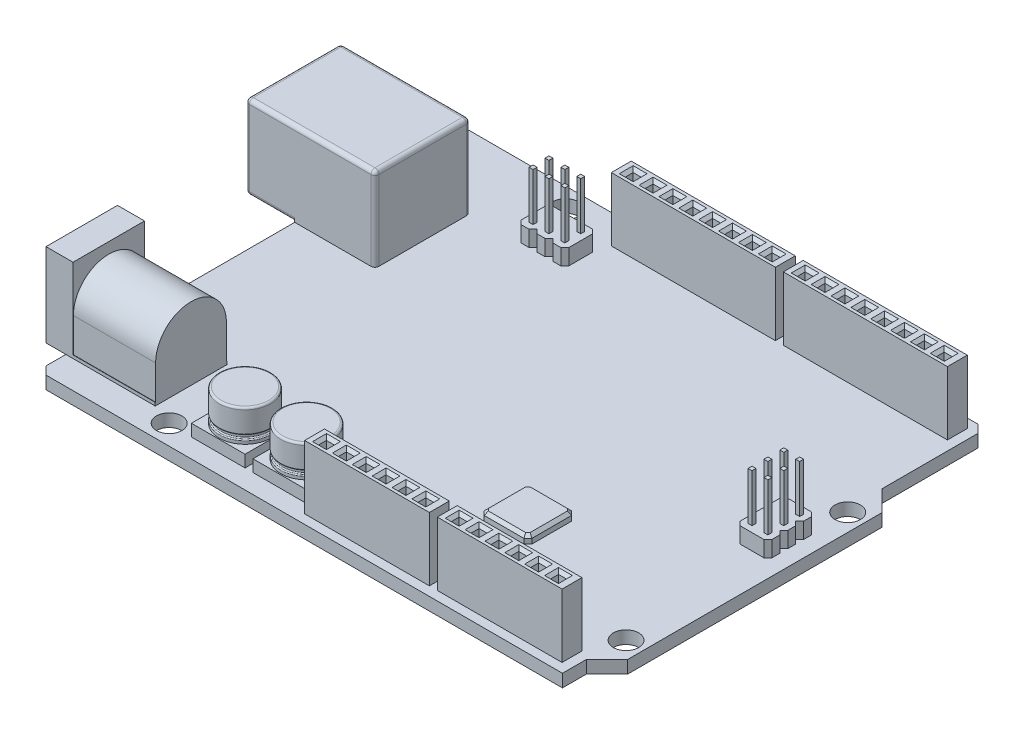
SolidWorks part; units mm, degrees
ref_plane "Front Plane" through (0, 0, 0) normal (0, 0, 1) x (1, 0, 0)
ref_plane "Top Plane" through (0, 0, 0) normal (0, 1, 0) x (1, 0, 0)
ref_plane "Right Plane" through (0, 0, 0) normal (1, 0, 0) x (0, 0, -1)
sketch "Sketch1" plane through (0, 0, 0) normal (0, 1, 0) x (1, 0, 0)
  line L0 (35.6, 10.95) -> (35.6, -21.05)
  line L1 (33, -26.65) -> (-32, -26.65)
  line L2 (33, -26.65) -> (33, -23.65)
  line L3 (32, 26.65) -> (-32, 26.65)
  line L4 (-33, -25.65) -> (-33, 25.65)
  line L5 (33, -26.65) -> (-33, 26.65) construction
  line L6 (33, 26.65) -> (-33, -26.65) construction
  line L7 (35.6, -21.05) -> (33, -23.65)
  line L8 (35.6, 10.95) -> (33, 13.55)
  line L9 (33, 13.55) -> (33, 25.65)
  line L10 (-32, -26.65) -> (-33, -25.65)
  line L11 (-33, 25.65) -> (-32, 26.65)
  line L12 (33, 25.65) -> (32, 26.65)
  line L13 (-19, 24.15) -> (-19, -24.15) construction
  circle A0 centre (-17.4, 24.15) radius 1.6
  circle A1 centre (-19, -24.15) radius 1.6
  circle A2 centre (33.4, -19.05) radius 1.6
  circle A3 centre (33.4, 8.85) radius 1.6
  point P0 (0, 0)
  dimension "D7" = 3.2
  dimension "D1" = 66
  dimension "D2" = 53.3
  dimension "D3" = 68.6
  dimension "D4" = 32
  dimension "D5" = 45
  dimension "D6" = 3
  dimension "D8" = 2.5
  dimension "D9" = 27.9
  dimension "D10" = 5.1
  dimension "D11" = 50.8
  dimension "D12" = 14
  dimension "D16" = 2.5
extrude "Boss-Extrude1" add sketch "Sketch1" along normal blind 1.6
sketch "Sketch2" plane through (0, 1.6, 0) normal (0, 1, 0) x (1, 0, 0)
  line L0 (-33, 25.65) -> (-33, -25.65) construction
  line L1 (-39.2, 17.65) -> (-22.9, 17.65)
  line L2 (-39.2, 17.65) -> (-39.2, 5.65)
  line L3 (-39.2, 5.65) -> (-22.9, 5.65)
  line L4 (-22.9, 17.65) -> (-22.9, 5.65)
  line L5 (32, 26.65) -> (-32, 26.65) construction
  line L6 (-32, -26.65) -> (33, -26.65) construction
  line L7 (-35.5, -14.15) -> (-21.75, -14.15)
  line L8 (-35.5, -14.15) -> (-35.5, -23.15)
  line L9 (-35.5, -23.15) -> (-21.75, -23.15)
  line L10 (-21.75, -14.15) -> (-21.75, -23.15)
  dimension "D1" = 16.3
  dimension "D2" = 12
  dimension "D3" = 6.2
  dimension "D4" = 9
  dimension "D5" = 9
  dimension "D6" = 13.75
  dimension "D7" = 2.5
  dimension "D8" = 3.5
extrude "Boss-Extrude2" add sketch "Sketch2" along normal blind 10.5
sketch "Sketch4" plane through (-39.2, 0, 0) normal (-1, 0, 0) x (0, 0, 1)
  line L0 (-11.65, 12.1) -> (-11.65, 1.6) construction
  line L1 (-17.65, 12.1) -> (-5.65, 12.1) construction
  line L2 (-17.65, 1.6) -> (-5.65, 1.6) construction
  line L3 (-7.15, 3.1) -> (-16.15, 3.1)
  line L4 (-16.15, 3.1) -> (-16.15, 8.1054)
  line L5 (-16.15, 8.1054) -> (-14.338, 10.6)
  line L6 (-14.338, 10.6) -> (-8.962, 10.6)
  line L7 (-8.962, 8.1054) -> (-14.338, 8.1054)
  line L8 (-14.338, 8.1054) -> (-14.338, 5.6054)
  line L9 (-14.338, 5.6054) -> (-8.962, 5.6054)
  line L10 (-8.962, 8.1054) -> (-8.962, 5.6054)
  line L11 (-7.15, 8.1054) -> (-8.962, 10.6)
  line L12 (-7.15, 3.1) -> (-7.15, 8.1054)
  point P16 (-11.65, 5.6054)
  point P17 (-11.65, 8.1054)
  point P18 (-11.65, 10.6)
  point P20 (-11.65, 3.1)
  dimension "D1" = 2.5
  dimension "D2" = 7.5
  dimension "D3" = 9
  dimension "D4" = 1.5
extrude "Cut-Extrude1" cut sketch "Sketch4" against normal blind 10
fillet "Fillet1" radius 0.5 11 edges at (-39.2, 12.1, -11.65) (-39.2, 1.6, -11.65) (-36.1, 1.6, -17.65) (-36.1, 1.6, -5.65) (-39.2, 6.85, -17.65) (-39.2, 6.85, -5.65) (-22.9, 6.85, -17.65) (-22.9, 6.85, -5.65) (-22.9, 12.1, -11.65) (-31.05, 12.1, -17.65) (-31.05, 12.1, -5.65)
sketch "Sketch5" plane through (-35.5, 0, 0) normal (-1, 0, 0) x (0, 0, 1)
  line L0 (18.65, 6.85) -> (14.15, 6.85) construction
  line L1 (14.15, 12.1) -> (14.15, 1.6) construction
  line L2 (18.65, 6.85) -> (18.65, 12.1) construction
  line L3 (14.15, 12.1) -> (23.15, 12.1) construction
  circle A0 centre (18.65, 6.85) radius 3.5
  circle A1 centre (18.65, 6.85) radius 0.5
  dimension "D1" = 7
  dimension "D2" = 1
extrude "Cut-Extrude2" cut sketch "Sketch5" against normal blind 10
sketch "Sketch6" plane through (-21.75, 0, 0) normal (1, 0, 0) x (0, 0, -1)
  line L0 (-18.65, 12.1) -> (-18.65, 1.6) construction
  line L1 (-23.15, 12.1) -> (-14.15, 12.1) construction
  line L2 (-23.15, 1.6) -> (-14.15, 1.6) construction
  line L3 (-23.1059, 6.2729) -> (-23.1059, 1.9995)
  line L4 (-23.15, 12.1) -> (-23.15, 1.6) construction
  line L5 (-23.15, 1.9995) -> (-23.15, 12.1)
  line L6 (-23.15, 12.1) -> (-14.15, 12.1)
  line L7 (-14.15, 1.9995) -> (-14.15, 12.1)
  line L9 (-23.1059, 1.9995) -> (-23.15, 1.9995)
  line L10 (-14.1941, 1.9995) -> (-14.15, 1.9995)
  line L11 (-14.1941, 6.2729) -> (-14.1941, 1.9995)
  arc A0 (-14.1941, 6.2729) -> (-23.1059, 6.2729) centre (-18.65, 6.2729) ccw
extrude "Cut-Extrude3" cut sketch "Sketch6" against normal offset from surface (10.35 mm away) 3.4 up to face at (-35.5, 6.85, 22.15)
fillet "Fillet2" radius 0.5 1 edges at (-35.5, 6.85, 19.15)
sketch "Sketch7" plane through (0, 1.6, 0) normal (0, 1, 0) x (1, 0, 0)
  line L0 (-10.5002, 24.25) -> (31.7998, 24.25) construction
  line L1 (-10.5002, 25.5) -> (10.1498, 25.5)
  line L2 (-10.5002, 25.5) -> (-10.5002, 23)
  line L3 (-10.5002, 23) -> (10.1498, 23)
  line L4 (10.1498, 25.5) -> (10.1498, 23)
  line L5 (11.1498, 25.5) -> (31.7998, 25.5)
  line L6 (11.1498, 25.5) -> (11.1498, 23)
  line L7 (11.1498, 23) -> (31.7998, 23)
  line L8 (31.7998, 25.5) -> (31.7998, 23)
  line L9 (-9.5002, 24.75) -> (-8.5002, 24.75)
  line L10 (-9.5002, 24.75) -> (-9.5002, 23.75)
  line L11 (-9.5002, 23.75) -> (-8.5002, 23.75)
  line L12 (-8.5002, 24.75) -> (-8.5002, 23.75)
  line L13 (12.1498, 24.75) -> (13.1498, 24.75)
  line L14 (12.1498, 24.75) -> (12.1498, 23.75)
  line L15 (12.1498, 23.75) -> (13.1498, 23.75)
  line L16 (13.1498, 24.75) -> (13.1498, 23.75)
  line L17 (-7.0002, 24.75) -> (-6.0002, 24.75)
  line L18 (-7.0002, 24.75) -> (-7.0002, 23.75)
  line L19 (-7.0002, 23.75) -> (-6.0002, 23.75)
  line L20 (-6.0002, 24.75) -> (-6.0002, 23.75)
  line L21 (14.6498, 24.75) -> (15.6498, 24.75)
  line L22 (14.6498, 24.75) -> (14.6498, 23.75)
  line L23 (14.6498, 23.75) -> (15.6498, 23.75)
  line L24 (15.6498, 24.75) -> (15.6498, 23.75)
  line L25 (-4.5002, 24.75) -> (-3.5002, 24.75)
  line L26 (-4.5002, 24.75) -> (-4.5002, 23.75)
  line L27 (-4.5002, 23.75) -> (-3.5002, 23.75)
  line L28 (-3.5002, 24.75) -> (-3.5002, 23.75)
  line L29 (17.1498, 24.75) -> (18.1498, 24.75)
  line L30 (17.1498, 24.75) -> (17.1498, 23.75)
  line L31 (17.1498, 23.75) -> (18.1498, 23.75)
  line L32 (18.1498, 24.75) -> (18.1498, 23.75)
  line L33 (-2.0002, 24.75) -> (-1.0002, 24.75)
  line L34 (-2.0002, 24.75) -> (-2.0002, 23.75)
  line L35 (-2.0002, 23.75) -> (-1.0002, 23.75)
  line L36 (-1.0002, 24.75) -> (-1.0002, 23.75)
  line L37 (19.6498, 24.75) -> (20.6498, 24.75)
  line L38 (19.6498, 24.75) -> (19.6498, 23.75)
  line L39 (19.6498, 23.75) -> (20.6498, 23.75)
  line L40 (20.6498, 24.75) -> (20.6498, 23.75)
  line L41 (0.4998, 24.75) -> (1.4998, 24.75)
  line L42 (0.4998, 24.75) -> (0.4998, 23.75)
  line L43 (0.4998, 23.75) -> (1.4998, 23.75)
  line L44 (1.4998, 24.75) -> (1.4998, 23.75)
  line L45 (22.1498, 24.75) -> (23.1498, 24.75)
  line L46 (22.1498, 24.75) -> (22.1498, 23.75)
  line L47 (22.1498, 23.75) -> (23.1498, 23.75)
  line L48 (23.1498, 24.75) -> (23.1498, 23.75)
  line L49 (2.9998, 24.75) -> (3.9998, 24.75)
  line L50 (2.9998, 24.75) -> (2.9998, 23.75)
  line L51 (2.9998, 23.75) -> (3.9998, 23.75)
  line L52 (3.9998, 24.75) -> (3.9998, 23.75)
  line L53 (24.6498, 24.75) -> (25.6498, 24.75)
  line L54 (24.6498, 24.75) -> (24.6498, 23.75)
  line L55 (24.6498, 23.75) -> (25.6498, 23.75)
  line L56 (25.6498, 24.75) -> (25.6498, 23.75)
  line L57 (5.4998, 24.75) -> (6.4998, 24.75)
  line L58 (5.4998, 24.75) -> (5.4998, 23.75)
  line L59 (5.4998, 23.75) -> (6.4998, 23.75)
  line L60 (6.4998, 24.75) -> (6.4998, 23.75)
  line L61 (27.1498, 24.75) -> (28.1498, 24.75)
  line L62 (27.1498, 24.75) -> (27.1498, 23.75)
  line L63 (27.1498, 23.75) -> (28.1498, 23.75)
  line L64 (28.1498, 24.75) -> (28.1498, 23.75)
  line L65 (7.9998, 24.75) -> (8.9998, 24.75)
  line L66 (7.9998, 24.75) -> (7.9998, 23.75)
  line L67 (7.9998, 23.75) -> (8.9998, 23.75)
  line L68 (8.9998, 24.75) -> (8.9998, 23.75)
  line L69 (29.6498, 24.75) -> (30.6498, 24.75)
  line L70 (29.6498, 24.75) -> (29.6498, 23.75)
  line L71 (29.6498, 23.75) -> (30.6498, 23.75)
  line L72 (30.6498, 24.75) -> (30.6498, 23.75)
  line L73 (-0.6002, -24.25) -> (31.7998, -24.25) construction
  line L74 (31.7998, -25.5) -> (16.0998, -25.5)
  line L75 (31.7998, -25.5) -> (31.7998, -23)
  line L76 (31.7998, -23) -> (16.0998, -23)
  line L77 (16.0998, -25.5) -> (16.0998, -23)
  line L78 (15.0998, -23) -> (-0.6002, -23)
  line L79 (15.0998, -23) -> (15.0998, -25.5)
  line L80 (15.0998, -25.5) -> (-0.6002, -25.5)
  line L81 (-0.6002, -23) -> (-0.6002, -25.5)
  line L82 (3.8998, -24.75) -> (2.8998, -24.75)
  line L83 (1.3998, -24.75) -> (0.3998, -24.75)
  line L84 (1.3998, -24.75) -> (1.3998, -23.75)
  line L85 (1.3998, -23.75) -> (0.3998, -23.75)
  line L86 (0.3998, -24.75) -> (0.3998, -23.75)
  line L87 (1.3998, -24.75) -> (0.3998, -23.75) construction
  line L88 (1.3998, -23.75) -> (0.3998, -24.75) construction
  line L89 (18.0998, -24.75) -> (17.0998, -24.75)
  line L90 (18.0998, -24.75) -> (18.0998, -23.75)
  line L91 (18.0998, -23.75) -> (17.0998, -23.75)
  line L92 (17.0998, -24.75) -> (17.0998, -23.75)
  line L93 (18.0998, -24.75) -> (17.0998, -23.75) construction
  line L94 (18.0998, -23.75) -> (17.0998, -24.75) construction
  line L95 (3.8998, -24.75) -> (3.8998, -23.75)
  line L96 (3.8998, -23.75) -> (2.8998, -23.75)
  line L97 (2.8998, -24.75) -> (2.8998, -23.75)
  line L98 (3.8998, -24.75) -> (2.8998, -23.75) construction
  line L99 (3.8998, -23.75) -> (2.8998, -24.75) construction
  line L100 (20.5998, -24.75) -> (19.5998, -24.75)
  line L101 (20.5998, -24.75) -> (20.5998, -23.75)
  line L102 (20.5998, -23.75) -> (19.5998, -23.75)
  line L103 (19.5998, -24.75) -> (19.5998, -23.75)
  line L104 (20.5998, -24.75) -> (19.5998, -23.75) construction
  line L105 (20.5998, -23.75) -> (19.5998, -24.75) construction
  line L106 (6.3998, -24.75) -> (5.3998, -24.75)
  line L107 (6.3998, -24.75) -> (6.3998, -23.75)
  line L108 (6.3998, -23.75) -> (5.3998, -23.75)
  line L109 (5.3998, -24.75) -> (5.3998, -23.75)
  line L110 (6.3998, -24.75) -> (5.3998, -23.75) construction
  line L111 (6.3998, -23.75) -> (5.3998, -24.75) construction
  line L112 (23.0998, -24.75) -> (22.0998, -24.75)
  line L113 (23.0998, -24.75) -> (23.0998, -23.75)
  line L114 (23.0998, -23.75) -> (22.0998, -23.75)
  line L115 (22.0998, -24.75) -> (22.0998, -23.75)
  line L116 (23.0998, -24.75) -> (22.0998, -23.75) construction
  line L117 (23.0998, -23.75) -> (22.0998, -24.75) construction
  line L118 (8.8998, -24.75) -> (7.8998, -24.75)
  line L119 (8.8998, -24.75) -> (8.8998, -23.75)
  line L120 (8.8998, -23.75) -> (7.8998, -23.75)
  line L121 (7.8998, -24.75) -> (7.8998, -23.75)
  line L122 (8.8998, -24.75) -> (7.8998, -23.75) construction
  line L123 (8.8998, -23.75) -> (7.8998, -24.75) construction
  line L124 (25.5998, -24.75) -> (24.5998, -24.75)
  line L125 (25.5998, -24.75) -> (25.5998, -23.75)
  line L126 (25.5998, -23.75) -> (24.5998, -23.75)
  line L127 (24.5998, -24.75) -> (24.5998, -23.75)
  line L128 (25.5998, -24.75) -> (24.5998, -23.75) construction
  line L129 (25.5998, -23.75) -> (24.5998, -24.75) construction
  line L130 (11.3998, -24.75) -> (10.3998, -24.75)
  line L131 (11.3998, -24.75) -> (11.3998, -23.75)
  line L132 (11.3998, -23.75) -> (10.3998, -23.75)
  line L133 (10.3998, -24.75) -> (10.3998, -23.75)
  line L134 (11.3998, -24.75) -> (10.3998, -23.75) construction
  line L135 (11.3998, -23.75) -> (10.3998, -24.75) construction
  line L136 (28.0998, -24.75) -> (27.0998, -24.75)
  line L137 (28.0998, -24.75) -> (28.0998, -23.75)
  line L138 (28.0998, -23.75) -> (27.0998, -23.75)
  line L139 (27.0998, -24.75) -> (27.0998, -23.75)
  line L140 (28.0998, -24.75) -> (27.0998, -23.75) construction
  line L141 (28.0998, -23.75) -> (27.0998, -24.75) construction
  line L142 (13.8998, -24.75) -> (12.8998, -24.75)
  line L143 (13.8998, -24.75) -> (13.8998, -23.75)
  line L144 (13.8998, -23.75) -> (12.8998, -23.75)
  line L145 (12.8998, -24.75) -> (12.8998, -23.75)
  line L146 (13.8998, -24.75) -> (12.8998, -23.75) construction
  line L147 (13.8998, -23.75) -> (12.8998, -24.75) construction
  line L148 (30.5998, -24.75) -> (29.5998, -24.75)
  line L149 (30.5998, -24.75) -> (30.5998, -23.75)
  line L150 (30.5998, -23.75) -> (29.5998, -23.75)
  line L151 (29.5998, -24.75) -> (29.5998, -23.75)
  line L152 (30.5998, -24.75) -> (29.5998, -23.75) construction
  line L153 (30.5998, -23.75) -> (29.5998, -24.75) construction
  point P85 (0.8998, -24.25)
  point P90 (17.5998, -24.25)
  point P97 (3.3998, -24.25)
  point P102 (20.0998, -24.25)
  point P107 (5.8998, -24.25)
  point P112 (22.5998, -24.25)
  point P117 (8.3998, -24.25)
  point P122 (25.0998, -24.25)
  point P127 (10.8998, -24.25)
  point P132 (27.5998, -24.25)
  point P137 (13.3998, -24.25)
  point P142 (30.0998, -24.25)
  dimension "D1" = 20.65
  dimension "D2" = 2.5
  dimension "D3" = 23
  dimension "D4" = 1
  dimension "D5" = 1
  dimension "D6" = 0.5
  dimension "D7" = 1
  dimension "D8" = 1
  dimension "D10" = 15.7
  dimension "D11" = 23
  dimension "D12" = 1
  dimension "D13" = 1
  dimension "D14" = 1
  dimension "D15" = 1
  dimension "D16" = 1
  dimension "D17" = 1
  dimension "D18" = 1
  dimension "D9" = 8
  dimension "D19" = 6
extrude "Boss-Extrude3" add sketch "Sketch7" along normal blind 8
chamfer "Chamfer1" distance 0.375 angle 45 112 edges at (12.1498, 9.6, -24.25) (12.6498, 9.6, -23.75) (13.1498, 9.6, -24.25) (12.6498, 9.6, -24.75) (-9.0002, 9.6, -23.75) (-9.5002, 9.6, -24.25) (-8.5002, 9.6, -24.25) (-9.0002, 9.6, -24.75) (30.6498, 9.6, -24.25) (30.1498, 9.6, -24.75) (29.6498, 9.6, -24.25) (30.1498, 9.6, -23.75) (28.1498, 9.6, -24.25) (27.6498, 9.6, -24.75) (27.1498, 9.6, -24.25) (27.6498, 9.6, -23.75) (25.6498, 9.6, -24.25) (25.1498, 9.6, -24.75) (24.6498, 9.6, -24.25) (25.1498, 9.6, -23.75) (20.6498, 9.6, -24.25) (20.1498, 9.6, -24.75) (19.6498, 9.6, -24.25) (20.1498, 9.6, -23.75) (23.1498, 9.6, -24.25) (22.6498, 9.6, -24.75) (22.1498, 9.6, -24.25) (22.6498, 9.6, -23.75) (18.1498, 9.6, -24.25) (17.6498, 9.6, -24.75) (17.1498, 9.6, -24.25) (17.6498, 9.6, -23.75) (15.6498, 9.6, -24.25) (15.1498, 9.6, -24.75) (14.6498, 9.6, -24.25) (15.1498, 9.6, -23.75) (8.9998, 9.6, -24.25) (8.4998, 9.6, -24.75) (7.9998, 9.6, -24.25) (8.4998, 9.6, -23.75) (6.4998, 9.6, -24.25) (5.9998, 9.6, -24.75) (5.4998, 9.6, -24.25) (5.9998, 9.6, -23.75) (3.9998, 9.6, -24.25) (3.4998, 9.6, -24.75) (2.9998, 9.6, -24.25) (3.4998, 9.6, -23.75) (1.4998, 9.6, -24.25) (0.9998, 9.6, -24.75) (0.4998, 9.6, -24.25) (0.9998, 9.6, -23.75) (-1.0002, 9.6, -24.25) (-1.5002, 9.6, -24.75) (-2.0002, 9.6, -24.25) (-1.5002, 9.6, -23.75) (-3.5002, 9.6, -24.25) (-4.0002, 9.6, -24.75) (-4.5002, 9.6, -24.25) (-4.0002, 9.6, -23.75) (-6.0002, 9.6, -24.25) (-6.5002, 9.6, -24.75) (-7.0002, 9.6, -24.25) (-6.5002, 9.6, -23.75) (13.3998, 9.6, 24.75) (13.8998, 9.6, 24.25) (13.3998, 9.6, 23.75) (12.8998, 9.6, 24.25) (10.8998, 9.6, 24.75) (11.3998, 9.6, 24.25) (10.8998, 9.6, 23.75) (10.3998, 9.6, 24.25) (8.3998, 9.6, 24.75) (8.8998, 9.6, 24.25) (8.3998, 9.6, 23.75) (7.8998, 9.6, 24.25) (5.8998, 9.6, 24.75) (6.3998, 9.6, 24.25) (5.8998, 9.6, 23.75) (5.3998, 9.6, 24.25) (3.3998, 9.6, 24.75) (3.8998, 9.6, 24.25) (3.3998, 9.6, 23.75) (2.8998, 9.6, 24.25) (0.8998, 9.6, 24.75) (1.3998, 9.6, 24.25) (0.8998, 9.6, 23.75) (0.3998, 9.6, 24.25) (30.5998, 9.6, 24.25) (30.0998, 9.6, 23.75) (29.5998, 9.6, 24.25) (30.0998, 9.6, 24.75) (28.0998, 9.6, 24.25) (27.5998, 9.6, 23.75) (27.0998, 9.6, 24.25) (27.5998, 9.6, 24.75) (25.5998, 9.6, 24.25) (25.0998, 9.6, 23.75) (24.5998, 9.6, 24.25) (25.0998, 9.6, 24.75) (23.0998, 9.6, 24.25) (22.5998, 9.6, 23.75) (22.0998, 9.6, 24.25) (22.5998, 9.6, 24.75) (20.5998, 9.6, 24.25) (20.0998, 9.6, 23.75) (19.5998, 9.6, 24.25) (20.0998, 9.6, 24.75) (18.0998, 9.6, 24.25) (17.5998, 9.6, 23.75) (17.0998, 9.6, 24.25) (17.5998, 9.6, 24.75)
sketch "Sketch8" plane through (0, 1.6, 0) normal (0, 1, 0) x (1, 0, 0)
  line L0 (-0.6002, -24.25) -> (-1.6002, -24.25) construction
  line L1 (-1.6002, -24.25) -> (-8.3502, -24.25)
  line L2 (-1.6002, -24.25) -> (-1.6002, -17.5)
  line L3 (-1.6002, -17.5) -> (-8.3502, -17.5)
  line L4 (-8.3502, -24.25) -> (-8.3502, -17.5)
  line L5 (-1.6002, -24.25) -> (-8.3502, -17.5) construction
  line L6 (-1.6002, -17.5) -> (-8.3502, -24.25) construction
  line L7 (-9.3502, -24.25) -> (-16.1002, -24.25)
  line L8 (-9.3502, -24.25) -> (-9.3502, -17.5)
  line L9 (-9.3502, -17.5) -> (-16.1002, -17.5)
  line L10 (-16.1002, -24.25) -> (-16.1002, -17.5)
  line L11 (-9.3502, -24.25) -> (-16.1002, -17.5) construction
  line L12 (-9.3502, -17.5) -> (-16.1002, -24.25) construction
  line L13 (-0.6002, -23) -> (-0.6002, -25.5) construction
  line L14 (-0.6002, -23) -> (-0.6002, -25.5) construction
  point P0 (-4.9752, -20.875)
  point P5 (-12.7252, -20.875)
  dimension "D1" = 6.75
  dimension "D2" = 1
  dimension "D3" = 1
extrude "Boss-Extrude4" add sketch "Sketch8" along normal blind 1.5
sketch "Sketch9" plane through (0, 3.1, 0) normal (0, 1, 0) x (1, 0, 0)
  line L0 (-12.7252, -17.5) -> (-12.7252, -20.875) construction
  line L1 (-9.3502, -17.5) -> (-16.1002, -17.5) construction
  line L2 (-16.1002, -20.875) -> (-12.7252, -20.875) construction
  line L3 (-16.1002, -17.5) -> (-16.1002, -24.25) construction
  line L4 (-4.9752, -17.5) -> (-4.9752, -20.875) construction
  line L5 (-1.6002, -17.5) -> (-8.3502, -17.5) construction
  circle A0 centre (-4.9752, -20.875) radius 3.25
  circle A1 centre (-12.7252, -20.875) radius 3.25
  dimension "D1" = 6.5
extrude "Boss-Extrude5" add sketch "Sketch9" along normal blind 4
fillet "Fillet3" radius 0.25 2 edges at (-12.7252, 7.1, 24.125) (-4.9752, 7.1, 24.125)
ref_plane "Plane1" through (0, 4.1, 0) normal (0, 1, 0) x (-1, 0, 0)
sketch "Sketch10" plane through (0, 4.1, 0) normal (0, 1, 0) x (-1, 0, 0)
  circle A0 centre (4.9752, 20.875) radius 3.25
  circle A1 centre (4.9752, 20.875) radius 3
  circle A2 centre (12.7252, 20.875) radius 3 construction
  circle A3 centre (12.7252, 20.875) radius 3.25 construction
  circle A4 centre (12.7252, 20.875) radius 3
  circle A5 centre (12.7252, 20.875) radius 3.25
  dimension "D1" = 6.5
  dimension "D2" = 6
extrude "Cut-Extrude4" cut sketch "Sketch10" against normal blind 0.5
fillet "Fillet4" radius 0.125 8 edges at (-4.9752, 3.6, 24.125) (-4.9752, 3.6, 23.875) (-4.9752, 4.1, 23.875) (-4.9752, 4.1, 24.125) (-12.7252, 4.1, 23.875) (-12.7252, 4.1, 24.125) (-12.7252, 3.6, 23.875) (-12.7252, 3.6, 24.125)
sketch "Sketch11" plane through (0, 1.6, 0) normal (0, 1, 0) x (1, 0, 0)
  line L0 (-16.5, 21.65) -> (-17, 21.15)
  line L1 (-15.5, 17.65) -> (-16.5, 17.65)
  line L2 (32, 26.65) -> (-32, 26.65) construction
  line L3 (-15.5, 21.65) -> (-16.5, 21.65)
  line L4 (-17, 18.15) -> (-17, 21.15)
  line L5 (-15, 17.65) -> (-17, 21.65) construction
  line L6 (-15, 21.65) -> (-17, 17.65) construction
  line L7 (-15, 21.15) -> (-15.5, 21.65)
  line L8 (-15.5, 17.65) -> (-15, 18.15)
  line L9 (-16.5, 17.65) -> (-17, 18.15)
  line L10 (-14.5, 21.65) -> (-15, 21.15)
  line L11 (-13.5, 17.65) -> (-14.5, 17.65)
  line L12 (-33, 25.65) -> (-33, 17.65) construction
  line L13 (-13.5, 21.65) -> (-14.5, 21.65)
  line L14 (30.1, 4.6066) -> (29.6, 4.1066)
  line L15 (-13, 17.65) -> (-15, 21.65) construction
  line L16 (-13, 21.65) -> (-15, 17.65) construction
  line L17 (-13, 21.15) -> (-13.5, 21.65)
  line L18 (-13.5, 17.65) -> (-13, 18.15)
  line L19 (-14.5, 17.65) -> (-15, 18.15)
  line L20 (-12.5, 21.65) -> (-13, 21.15)
  line L21 (-11.5, 17.65) -> (-12.5, 17.65)
  line L22 (-11, 18.15) -> (-11, 21.15)
  line L23 (-11.5, 21.65) -> (-12.5, 21.65)
  line L25 (-11, 17.65) -> (-13, 21.65) construction
  line L26 (-11, 21.65) -> (-13, 17.65) construction
  line L27 (-11, 21.15) -> (-11.5, 21.65)
  line L28 (-11.5, 17.65) -> (-11, 18.15)
  line L29 (-12.5, 17.65) -> (-13, 18.15)
  line L30 (35.6, -21.05) -> (35.6, 10.95) construction
  line L31 (33.6, 3.1066) -> (33.6, 4.1066)
  line L32 (33.1, 4.6066) -> (30.1, 4.6066)
  line L33 (29.6, 3.1066) -> (29.6, 4.1066)
  line L34 (33.6, 2.6066) -> (29.6, 4.6066) construction
  line L35 (33.6, 4.6066) -> (29.6, 2.6066) construction
  line L36 (30.1, 2.6066) -> (29.6, 3.1066)
  line L37 (33.6, 3.1066) -> (33.1, 2.6066)
  line L38 (33.6, 4.1066) -> (33.1, 4.6066)
  line L39 (30.1, 2.6066) -> (29.6, 2.1066)
  line L41 (33.6, 1.1066) -> (33.6, 2.1066)
  line L43 (29.6, 1.1066) -> (29.6, 2.1066)
  line L44 (33.6, 0.6066) -> (29.6, 2.6066) construction
  line L45 (33.6, 2.6066) -> (29.6, 0.6066) construction
  line L46 (30.1, 0.6066) -> (29.6, 1.1066)
  line L47 (33.6, 1.1066) -> (33.1, 0.6066)
  line L48 (33.6, 2.1066) -> (33.1, 2.6066)
  line L49 (30.1, 0.6066) -> (29.6, 0.1066)
  line L50 (33.1, -1.3934) -> (30.1, -1.3934)
  line L51 (33.6, -0.8934) -> (33.6, 0.1066)
  line L53 (29.6, -0.8934) -> (29.6, 0.1066)
  line L54 (33.6, -1.3934) -> (29.6, 0.6066) construction
  line L55 (33.6, 0.6066) -> (29.6, -1.3934) construction
  line L56 (30.1, -1.3934) -> (29.6, -0.8934)
  line L57 (33.6, -0.8934) -> (33.1, -1.3934)
  line L58 (33.6, 0.1066) -> (33.1, 0.6066)
  point P0 (-16, 19.65)
  point P13 (-14, 19.65)
  point P26 (-12, 19.65)
  point P39 (31.6, 3.6066)
  point P52 (31.6, 1.6066)
  point P65 (31.6, -0.3934)
  dimension "D2" = 4
  dimension "D3" = 0.5
  dimension "D8" = 4
  dimension "D9" = 0.5
  dimension "D10" = 0.5
  dimension "D11" = 0.5
  dimension "D12" = 0.5
  dimension "D13" = 0.5
  dimension "D14" = 4
  dimension "D15" = 0.5
  dimension "D16" = 4
  dimension "D17" = 0.5
  dimension "D18" = 0.5
  dimension "D19" = 0.5
  dimension "D20" = 0.5
  dimension "D21" = 0.5
  dimension "D23" = 7
  dimension "D24" = 19
  dimension "D28" = 0.5
  dimension "D29" = 0.5
  dimension "D30" = 0.5
  dimension "D31" = 0.5
  dimension "D32" = 0.5
  dimension "D33" = 0.5
  dimension "D34" = 0.5
  dimension "D35" = 0.5
  dimension "D36" = 4
  dimension "D38" = 0.5
  dimension "D39" = 0.5
  dimension "D40" = 0.5
  dimension "D41" = 0.5
  dimension "D42" = 0.5
  dimension "D43" = 0.5
  dimension "D44" = 0.5
  dimension "D45" = 0.5
extrude "Boss-Extrude7" add sketch "Sketch11" along normal blind 2
sketch "Sketch12" plane through (0, 3.6, 0) normal (0, 1, 0) x (1, 0, 0)
  line L0 (-16, 21.65) -> (-16, 17.65) construction
  line L1 (-15.75, 20.4) -> (-16.25, 20.4)
  line L2 (-15.75, 20.4) -> (-15.75, 20.9)
  line L3 (-15.75, 20.9) -> (-16.25, 20.9)
  line L4 (-16.25, 20.4) -> (-16.25, 20.9)
  line L5 (-15.75, 20.4) -> (-16.25, 20.9) construction
  line L6 (-15.75, 20.9) -> (-16.25, 20.4) construction
  line L7 (-15.75, 18.4) -> (-16.25, 18.9) construction
  line L8 (-15.75, 18.9) -> (-16.25, 18.4) construction
  line L9 (-16.25, 18.9) -> (-16.25, 18.4)
  line L10 (-15.75, 18.4) -> (-16.25, 18.4)
  line L11 (-15.75, 18.9) -> (-15.75, 18.4)
  line L12 (-15.75, 18.9) -> (-16.25, 18.9)
  line L13 (-15.5, 21.65) -> (-16.5, 21.65) construction
  line L14 (-16.5, 17.65) -> (-15.5, 17.65) construction
  line L15 (-17, 19.65) -> (-11, 19.65) construction
  line L16 (-17, 21.15) -> (-17, 18.15) construction
  line L17 (-11, 18.15) -> (-11, 21.15) construction
  line L18 (-13.75, 20.4) -> (-14.25, 20.4)
  line L19 (-13.75, 20.4) -> (-13.75, 20.9)
  line L20 (-13.75, 20.9) -> (-14.25, 20.9)
  line L21 (-14.25, 20.4) -> (-14.25, 20.9)
  line L22 (-14.25, 18.9) -> (-14.25, 18.4)
  line L23 (-13.75, 18.4) -> (-14.25, 18.4)
  line L24 (-13.75, 18.9) -> (-13.75, 18.4)
  line L25 (-13.75, 18.9) -> (-14.25, 18.9)
  line L26 (-13.75, 20.4) -> (-14.25, 20.9) construction
  line L27 (-13.75, 20.9) -> (-14.25, 20.4) construction
  line L28 (-13.75, 18.4) -> (-14.25, 18.9) construction
  line L29 (-13.75, 18.9) -> (-14.25, 18.4) construction
  line L30 (-11.75, 20.4) -> (-12.25, 20.4)
  line L31 (-11.75, 20.4) -> (-11.75, 20.9)
  line L32 (-11.75, 20.9) -> (-12.25, 20.9)
  line L33 (-12.25, 20.4) -> (-12.25, 20.9)
  line L34 (-12.25, 18.9) -> (-12.25, 18.4)
  line L35 (-11.75, 18.4) -> (-12.25, 18.4)
  line L36 (-11.75, 18.9) -> (-11.75, 18.4)
  line L37 (-11.75, 18.9) -> (-12.25, 18.9)
  line L38 (-11.75, 20.4) -> (-12.25, 20.9) construction
  line L39 (-11.75, 20.9) -> (-12.25, 20.4) construction
  line L40 (-11.75, 18.4) -> (-12.25, 18.9) construction
  line L41 (-11.75, 18.9) -> (-12.25, 18.4) construction
  line L42 (31.6, 4.6066) -> (31.6, -1.3934) construction
  line L43 (33.1, 4.6066) -> (30.1, 4.6066) construction
  line L44 (30.1, -1.3934) -> (33.1, -1.3934) construction
  line L45 (33.6, 3.6066) -> (29.6, 3.6066) construction
  line L46 (33.6, 3.1066) -> (33.6, 4.1066) construction
  line L47 (29.6, 4.1066) -> (29.6, 3.1066) construction
  line L48 (30.35, 3.8566) -> (30.85, 3.3566) construction
  line L49 (32.85, 3.3566) -> (32.35, 3.3566)
  line L50 (32.85, 3.3566) -> (32.85, 3.8566)
  line L51 (32.85, 3.8566) -> (32.35, 3.8566)
  line L52 (32.35, 3.3566) -> (32.35, 3.8566)
  line L53 (32.85, 3.3566) -> (32.35, 3.8566) construction
  line L54 (32.85, 3.8566) -> (32.35, 3.3566) construction
  line L55 (30.35, 3.3566) -> (30.85, 3.8566) construction
  line L56 (30.85, 3.3566) -> (30.85, 3.8566)
  line L57 (30.35, 3.8566) -> (30.85, 3.8566)
  line L58 (30.35, 3.3566) -> (30.35, 3.8566)
  line L59 (30.35, 3.3566) -> (30.85, 3.3566)
  line L60 (32.85, 1.3566) -> (32.35, 1.3566)
  line L61 (32.85, 1.3566) -> (32.85, 1.8566)
  line L62 (32.85, 1.8566) -> (32.35, 1.8566)
  line L63 (32.35, 1.3566) -> (32.35, 1.8566)
  line L64 (30.85, 1.3566) -> (30.85, 1.8566)
  line L65 (30.35, 1.8566) -> (30.85, 1.8566)
  line L66 (30.35, 1.3566) -> (30.35, 1.8566)
  line L67 (30.35, 1.3566) -> (30.85, 1.3566)
  line L68 (30.35, 1.8566) -> (30.85, 1.3566) construction
  line L69 (32.85, 1.3566) -> (32.35, 1.8566) construction
  line L70 (32.85, 1.8566) -> (32.35, 1.3566) construction
  line L71 (30.35, 1.3566) -> (30.85, 1.8566) construction
  line L72 (32.85, -0.6434) -> (32.35, -0.6434)
  line L73 (32.85, -0.6434) -> (32.85, -0.1434)
  line L74 (32.85, -0.1434) -> (32.35, -0.1434)
  line L75 (32.35, -0.6434) -> (32.35, -0.1434)
  line L76 (30.85, -0.6434) -> (30.85, -0.1434)
  line L77 (30.35, -0.1434) -> (30.85, -0.1434)
  line L78 (30.35, -0.6434) -> (30.35, -0.1434)
  line L79 (30.35, -0.6434) -> (30.85, -0.6434)
  line L80 (30.35, -0.1434) -> (30.85, -0.6434) construction
  line L81 (32.85, -0.6434) -> (32.35, -0.1434) construction
  line L82 (32.85, -0.1434) -> (32.35, -0.6434) construction
  line L83 (30.35, -0.6434) -> (30.85, -0.1434) construction
  point P0 (-16, 20.65)
  point P9 (-16, 18.65)
  point P23 (-14, 20.65)
  point P32 (-14, 18.65)
  point P33 (-12, 20.65)
  point P42 (-12, 18.65)
  point P54 (32.6, 3.6066)
  point P63 (30.6, 3.6066)
  point P65 (32.6, 1.6066)
  point P74 (30.6, 1.6066)
  point P75 (32.6, -0.3934)
  point P84 (30.6, -0.3934)
  dimension "D1" = 0.5
  dimension "D2" = 2
  dimension "D4" = 0.5
  dimension "D5" = 2
  dimension "D3" = 3
  dimension "D6" = 3
extrude "Boss-Extrude8" add sketch "Sketch12" along normal up to surface (6 mm away) up to face at (8.4998, 9.6, -24.25)
sketch "Sketch13" plane through (0, 1.6, 0) normal (0, 1, 0) x (1, 0, 0)
  line L0 (17, -9.5) -> (16.5, -9)
  line L1 (16.5, -15) -> (11.5, -15)
  line L2 (17, -14.5) -> (17, -9.5)
  line L3 (16.5, -9) -> (11.5, -9)
  line L4 (11, -14.5) -> (11, -9.5)
  line L5 (17, -15) -> (11, -9) construction
  line L6 (17, -9) -> (11, -15) construction
  line L7 (16.5, -15) -> (17, -14.5)
  line L8 (11.5, -15) -> (11, -14.5)
  line L9 (11, -9.5) -> (11.5, -9)
  point P0 (14, -12)
  dimension "D1" = 6
  dimension "D2" = 12
  dimension "D3" = 14
extrude "Boss-Extrude9" add sketch "Sketch13" along normal blind 1
chamfer "Chamfer2" distance 0.375 angle 45 8 edges at (16.75, 2.6, 9.25) (17, 2.6, 12) (16.75, 2.6, 14.75) (14, 2.6, 15) (11.25, 2.6, 14.75) (11, 2.6, 12) (11.25, 2.6, 9.25) (14, 2.6, 9)
